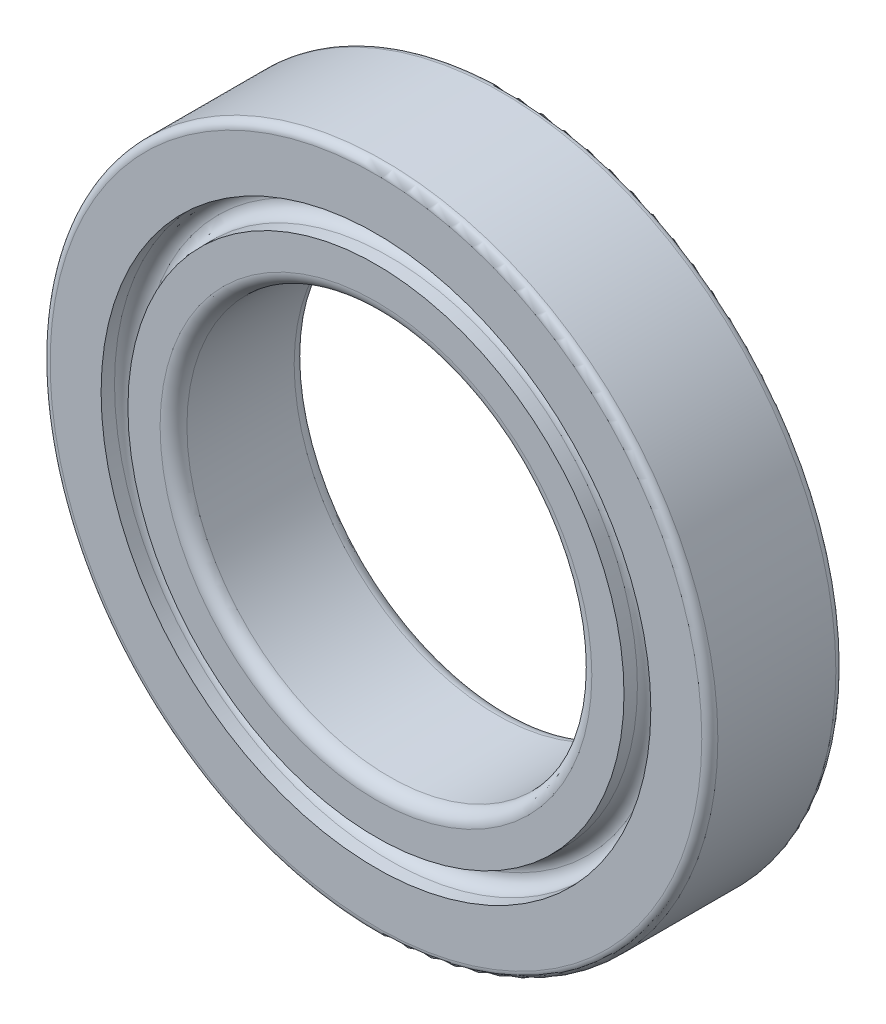
SolidWorks part; units mm, degrees
ref_plane "Front Plane" through (0, 0, 0) normal (0, 0, 1) x (1, 0, 0)
ref_plane "Top Plane" through (0, 0, 0) normal (0, 1, 0) x (1, 0, 0)
ref_plane "Right Plane" through (0, 0, 0) normal (1, 0, 0) x (0, 0, -1)
sketch "Sketch1" plane through (0, 0, 0) normal (0, 0, 1) x (1, 0, 0)
  circle A0 centre (0, 0) radius 12.45
  dimension "D1" = 24.9
extrude "Boss-Extrude1" add sketch "Sketch1" along normal blind 5
sketch "Sketch2" plane through (0, 0, 5) normal (0, 0, 1) x (1, 0, 0)
  circle A0 centre (0, 0) radius 7.55
  dimension "D1" = 15.1
extrude "Cut-Extrude1" cut sketch "Sketch2" against normal through all
fillet "Fillet1" radius 0.5 2 edges at (7.55, 0, 0) (7.55, 0, 5)
sketch "Sketch3" plane through (0, 0, 5) normal (0, 0, 1) x (1, 0, 0)
  circle A0 centre (0, 0) radius 9.25
  circle A1 centre (0, 0) radius 10.25
  dimension "D1" = 18.5
  dimension "D2" = 1
extrude "Cut-Extrude2" cut sketch "Sketch3" against normal blind 1 contours A1 | A0
fillet "Fillet2" radius 0.5 2 edges at (10.25, 0, 4) (9.25, 0, 4)
sketch "Sketch4" plane through (0, 0, 0) normal (0, 0, -1) x (-1, 0, 0)
  circle A0 centre (0, 0) radius 9.25
  circle A1 centre (0, 0) radius 10.25
  dimension "D1" = 18.5
  dimension "D2" = 1
extrude "Cut-Extrude3" cut sketch "Sketch4" against normal blind 1 contours A1 | A0
fillet "Fillet3" radius 0.5 2 edges at (-10.25, 0, 1) (-9.25, 0, 1)
fillet "Fillet4" radius 0.3 2 edges at (12.45, 0, 5) (12.45, 0, 0)
